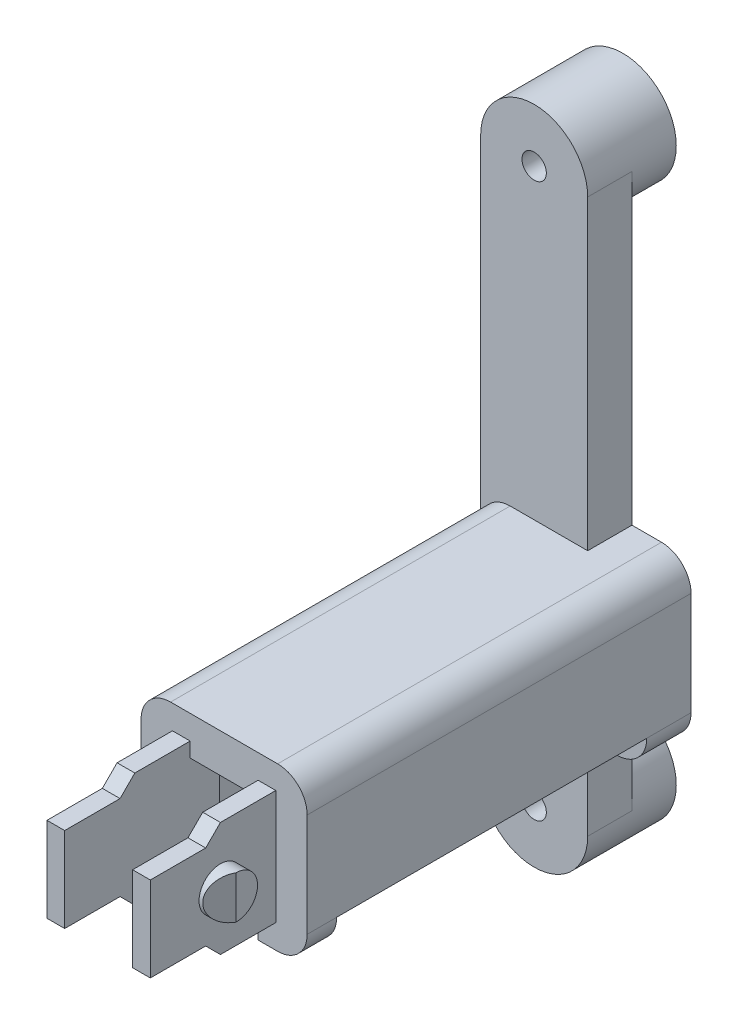
SolidWorks part; units mm, degrees
material "PET"
ref_plane "Front Plane" through (0, 0, 0) normal (0, 0, 1) x (1, 0, 0)
ref_plane "Top Plane" through (0, 0, 0) normal (0, 1, 0) x (1, 0, 0)
ref_plane "Right Plane" through (0, 0, 0) normal (1, 0, 0) x (0, 0, -1)
sketch "Sketch1" plane through (0, 0, 0) normal (0, 0, 1) x (1, 0, 0)
  line L29 (15.25, 29.5) -> (15.25, 15.5)
  line L30 (11.25, 33.5) -> (7.25, 33.5)
  line L31 (-7.25, 0) -> (-7.25, 75)
  line L33 (7.25, 11.5) -> (11.25, 11.5)
  line L34 (7.25, 0) -> (7.25, 11.5)
  line L36 (7.25, 33.5) -> (7.25, 75)
  arc A2 (11.25, 33.5) -> (15.25, 29.5) centre (11.25, 29.5) cw
  circle A8 centre (0, 0) radius 1.65
  circle A9 centre (0, 75) radius 1.65
  arc A10 (7.25, 75) -> (-7.25, 75) centre (0, 75) ccw
  arc A11 (-7.25, 0) -> (7.25, 0) centre (0, 0) ccw
  arc A12 (11.25, 11.5) -> (15.25, 15.5) centre (11.25, 15.5) ccw
extrude "Boss-Extrude1" add sketch "Sketch1" along normal blind 75
sketch "Sketch7" plane through (0, 0, 0) normal (0, 0, -1) x (-1, 0, 0)
  line L0 (-7.25, 75) -> (-7.25, 33.5)
  line L1 (-7.25, 33.5) -> (-11.25, 33.5)
  line L2 (-15.25, 29.5) -> (-15.25, 15.5)
  line L7 (-11.25, 11.5) -> (-7.25, 11.5)
  line L8 (-7.25, 11.5) -> (-7.25, 0)
  line L10 (7.25, 0) -> (7.25, 75)
  arc A0 (-7.25, 75) -> (7.25, 75) centre (0, 75) ccw
  arc A1 (7.25, 0) -> (-7.25, 0) centre (0, 0) ccw
  arc A2 (-11.25, 33.5) -> (-15.25, 29.5) centre (-11.25, 29.5) ccw
  arc A3 (-15.25, 15.5) -> (-11.25, 11.5) centre (-11.25, 15.5) ccw
  circle A4 centre (0, 75) radius 3
  circle A5 centre (0, 0) radius 3
extrude "Cut-Extrude6" cut sketch "Sketch7" against normal blind 6
sketch "Sketch14" plane through (0, 0, 75) normal (0, 0, 1) x (1, 0, 0)
  line L0 (-0.6, 28.25) -> (8.6, 28.25)
  line L1 (-0.6, 28.25) -> (-0.6, 11.5)
  line L2 (7.25, 11.5) -> (8.6, 11.5)
  line L3 (8.6, 28.25) -> (8.6, 11.5)
  line L4 (-7.25, 15.5) -> (-7.25, 0)
  line L5 (7.25, 0) -> (7.25, 11.5)
  line L6 (-3.25, 11.5) -> (-0.6, 11.5)
  line L7 (7.25, 33.5) -> (-3.25, 33.5)
  line L8 (7.25, 33.5) -> (7.25, 75)
  line L9 (-7.25, 29.5) -> (-7.25, 75)
  arc A0 (-7.25, 15.5) -> (-3.25, 11.5) centre (-3.25, 15.5) ccw
  arc A1 (-7.25, 0) -> (7.25, 0) centre (0, 0) ccw
  arc A2 (7.25, 75) -> (-7.25, 75) centre (0, 75) ccw
  arc A3 (-3.25, 33.5) -> (-7.25, 29.5) centre (-3.25, 29.5) ccw
extrude "Cut-Extrude12" cut sketch "Sketch14" against normal offset from surface (63 mm away) 6 up to face at (6.9157, 28.5, 6)
sketch "Sketch9" plane through (15.25, 0, 0) normal (1, 0, 0) x (0, 0, -1)
  line L8 (-75, 33.5) -> (-58, 33.5)
  line L9 (-75, 33.5) -> (-75, 11.5)
  line L10 (-75, 11.5) -> (-58, 11.5)
  line L11 (-58, 33.5) -> (-58, 11.5)
  circle A1 centre (-65.5, 22.5) radius 2.9
extrude "Cut-Extrude8" cut sketch "Sketch9" against normal offset from surface (4.25 mm away) 2.4 up to face at (8.6, 19.875, 43.5)
sketch "Sketch10" plane through (-7.25, 0, 0) normal (-1, 0, 0) x (0, 0, 1)
  line L1 (75, 33.5) -> (75, 11.5)
  line L4 (58, 33.5) -> (58, 11.5)
  line L5 (75, 11.5) -> (58, 11.5)
  line L6 (75, 33.5) -> (58, 33.5)
  circle A1 centre (65.5, 22.5) radius 2.9
extrude "Cut-Extrude9" cut sketch "Sketch10" against normal offset from surface (4.25 mm away) 2.4 up to face at (-0.6, 19.875, 43.5)
sketch "Sketch11" plane through (0, 0, 75) normal (0, 0, 1) x (1, 0, 0)
  line L0 (-7.25, 14.75) -> (-7.25, 11.5)
  line L1 (-7.25, 11.5) -> (15.25, 11.5)
  line L2 (-7.25, 33.5) -> (15.25, 33.5)
  line L3 (15.25, 11.5) -> (15.25, 14.75)
  line L4 (-7.25, 33.5) -> (-7.25, 30.25)
  line L5 (15.25, 33.5) -> (15.25, 30.25)
  line L6 (-0.6, 14.75) -> (-0.6, 30.25)
  line L7 (8.6, 14.75) -> (8.6, 30.25)
  line L8 (-7.25, 14.75) -> (-0.6, 14.75)
  line L9 (15.25, 14.75) -> (8.6, 14.75)
  line L10 (-7.25, 30.25) -> (-0.6, 30.25)
  line L11 (15.25, 30.25) -> (8.6, 30.25)
extrude "Cut-Extrude10" cut sketch "Sketch11" against normal up to surface (17 mm away) up to face at (-4.7761, 22.5, 58)
sketch "Sketch12" plane through (-7.25, 0, 0) normal (-1, 0, 0) x (0, 0, 1)
  line L0 (65.5, 30.25) -> (67.5, 28.25)
  line L1 (67.5, 28.25) -> (75, 28.25)
  line L2 (65.5, 14.75) -> (67.5, 16.75)
  line L3 (67.5, 16.75) -> (75, 16.75)
  line L4 (65.5, 30.25) -> (75, 30.25)
  line L5 (75, 30.25) -> (75, 28.25)
  line L6 (65.5, 14.75) -> (75, 14.75)
  line L7 (75, 14.75) -> (75, 16.75)
extrude "Cut-Extrude11" cut sketch "Sketch12" against normal up to surface (22.5 mm away) up to face at (15.25, 22.5, 32)
sketch "Sketch13" plane through (0, 33.5, 0) normal (0, 1, 0) x (1, 0, 0)
  line L0 (-5.1, -65.5) -> (-3.5, -68.4)
  line L1 (-5.125, -62.6) -> (-5.1, -65.5)
  line L2 (13.1, -65.5) -> (11.5, -68.4)
  line L3 (-7.25, -62.6) -> (-5.125, -62.6)
  line L4 (-7.25, -62.6) -> (-7.25, -68.4)
  line L5 (-7.25, -68.4) -> (-3.5, -68.4)
  line L6 (13.125, -62.6) -> (13.1, -65.5)
  line L7 (15.25, -62.6) -> (13.125, -62.6)
  line L8 (11.5, -68.4) -> (15.25, -68.4)
  line L9 (15.25, -68.4) -> (15.25, -62.6)
extrude "Cut-Extrude13" cut sketch "Sketch13" against normal up to surface (22 mm away) up to face at (9.0333, 11.5, 25.3333)
sketch "Sketch15" plane through (0, 0, 12) normal (0, 0, 1) x (1, 0, 0)
  line L0 (-3.25, 11.5) -> (11.25, 11.5)
  line L2 (-7.25, 15.5) -> (-5.25, 15.5)
  line L4 (13.25, 15.5) -> (15.25, 15.5)
  line L9 (-3.25, 31.5) -> (11.25, 31.5)
  line L10 (-5.25, 29.5) -> (-5.25, 15.5)
  line L12 (13.25, 29.5) -> (13.25, 15.5)
  arc A0 (11.25, 31.5) -> (13.25, 29.5) centre (11.25, 29.5) cw
  arc A1 (-3.25, 31.5) -> (-5.25, 29.5) centre (-3.25, 29.5) ccw
  arc A2 (-7.25, 15.5) -> (-3.25, 11.5) centre (-3.25, 15.5) ccw
  arc A3 (11.25, 11.5) -> (15.25, 15.5) centre (11.25, 15.5) ccw
extrude "Cut-Extrude14" cut sketch "Sketch15" along normal offset from surface (42 mm away) 4 up to face at (4, 21.975, 58)
